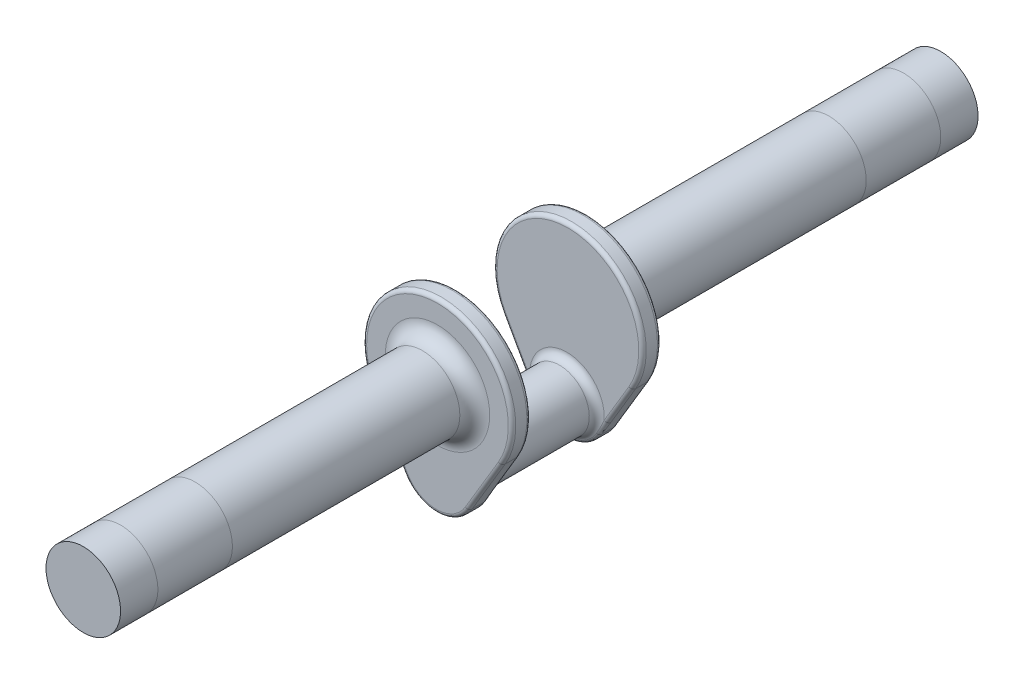
SolidWorks part; units mm, degrees
material "Alloy Steel"
ref_plane "Front" through (0, 0, 0) normal (0, 0, 1) x (1, 0, 0)
ref_plane "Top" through (0, 0, 0) normal (0, 1, 0) x (1, 0, 0)
ref_plane "Right" through (0, 0, 0) normal (1, 0, 0) x (0, 0, -1)
sketch "Sketch1" plane through (0, 0, 0) normal (0, 0, 1) x (1, 0, 0)
  line L1 (-22.1747, -12.3872) -> (-11.4456, -31.5936)
  line L2 (21.8165, -13.0077) -> (10.55, -31.9039)
  arc A0 (21.8165, -13.0077) -> (-22.1747, -12.3872) centre (0, 0) ccw
  arc A1 (-11.4456, -31.5936) -> (10.55, -31.9039) centre (-0.3582, -25.4) ccw
  dimension "D1" = 25.4
  dimension "D2" = 12.7
  dimension "D3" = 25.4
extrude "Extrude1" add sketch "Sketch1" along normal blind 6.35
sketch "Sketch2" plane through (0, 0, 0) normal (0, 0, -1) x (-1, 0, 0)
  circle A0 centre (0, 0) radius 12.7
  dimension "D1" = 25.4
extrude "Extrude2" add sketch "Sketch2" along normal blind 120.65
sketch "Sketch3" plane through (0, 0, 6.35) normal (0, 0, 1) x (1, 0, 0)
  circle A2 centre (-0.3582, -25.4) radius 10.16
  dimension "D1" = 20.32
extrude "Extrude4" add sketch "Sketch3" along normal blind 19.05
fillet "Fillet1" radius 2.54 1 edges at (9.8018, -25.4, 6.35)
fillet "Fillet2" radius 5.08 1 edges at (12.7, 0, 0)
fillet "Fillet3" radius 1.27 8 edges at (16.1833, -22.4558, 6.35) (-16.8101, -21.9904, 6.35) (16.1833, -22.4558, 0) (-0.5373, -38.0987, 0) (-16.8101, -21.9904, 0) (0.3582, 25.3975, 6.35) (0.3582, 25.3975, 0) (-0.5373, -38.0987, 6.35)
ref_plane "Plane3" through (0, 0, -107.95) normal (0, 0, -1) x (-1, 0, 0)
ref_plane "Plane4" through (0, 0, -82.55) normal (0, 0, -1) x (-1, 0, 0)
sketch "Sketch5" plane through (0, 0, 0) normal (0, 1, 0) x (1, 0, 0)
  line L0 (-48.6529, 82.55) -> (48.6529, 82.55)
  line L1 (13.97, 82.55) -> (-13.97, 82.55) construction
split line "Split Line4"
sketch "Sketch6" plane through (0, 0, 0) normal (0, 1, 0) x (1, 0, 0)
  line L0 (-27.9735, 107.95) -> (32.6427, 107.95)
  line L1 (13.97, 107.95) -> (-13.97, 107.95) construction
split line "Split Line5"
mirror "Mirror2" about plane through (-0.3582, -25.4, 25.4) normal (0, 0, 1) of bodies 103
ref_axis "Axis1" through (0, 0, 133.35) along (0, 0, -1)
sketch "Sketch7" plane through (0, 0, 0) normal (0, 1, 0) x (1, 0, 0)
  line L0 (0, -146.05) -> (0, 95.25)
  line L1 (0, -133.35) -> (0, -55.88) construction
  line L2 (-12.7, -158.75) -> (12.7, -158.75) construction
  line L3 (-12.7, 107.95) -> (12.7, 107.95) construction
  dimension "D1" = 12.7
  dimension "D2" = 12.7
